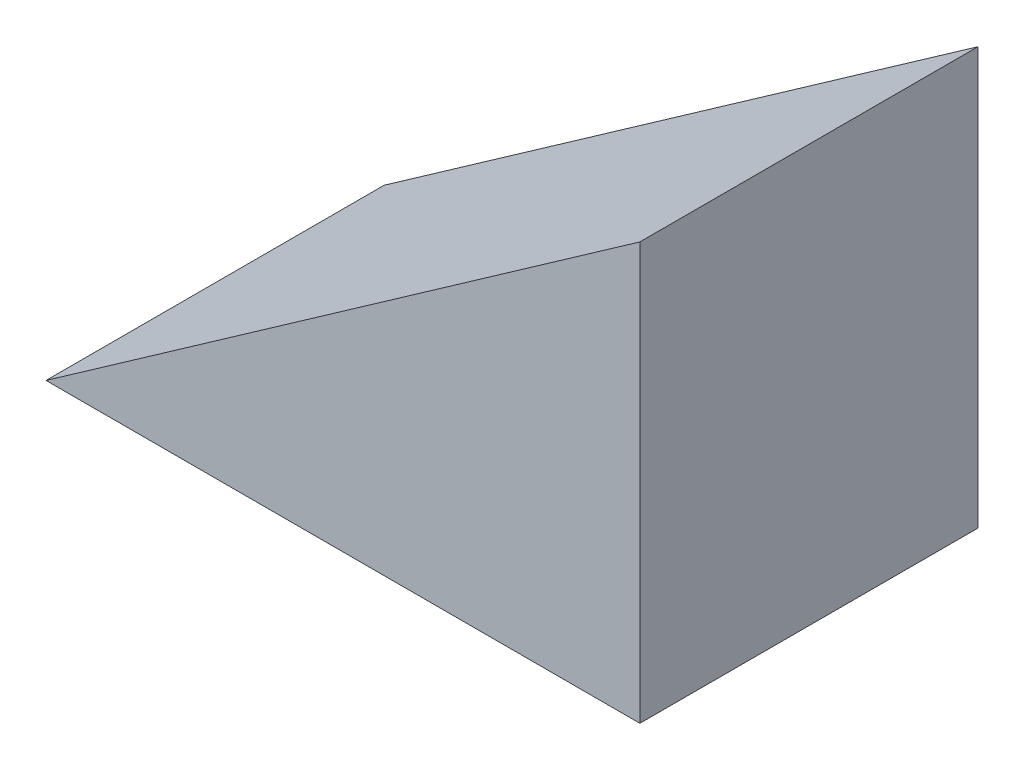
SolidWorks part; units mm, degrees
ref_plane "Front Plane" through (0, 0, 0) normal (0, 0, 1) x (1, 0, 0)
ref_plane "Top Plane" through (0, 0, 0) normal (0, 1, 0) x (1, 0, 0)
ref_plane "Right Plane" through (0, 0, 0) normal (1, 0, 0) x (0, 0, -1)
sketch "Sketch1" plane through (0, 0, 0) normal (0, 1, 0) x (1, 0, 0)
  line L1 (-52.25, -29.75) -> (52.25, -29.75)
  line L2 (-52.25, -29.75) -> (-52.25, 29.75)
  line L3 (-52.25, 29.75) -> (52.25, 29.75)
  line L4 (52.25, -29.75) -> (52.25, 29.75)
  line L5 (-52.25, -29.75) -> (52.25, 29.75) construction
  line L6 (-52.25, 29.75) -> (52.25, -29.75) construction
  point P0 (0, 0)
  dimension "D1" = 104.5
  dimension "D2" = 59.5
extrude "Boss-Extrude1" add sketch "Sketch1" along normal blind 73.36
sketch "Sketch6" plane through (0, 0, 29.75) normal (0, 0, 1) x (1, 0, 0)
  line L0 (-52.25, 0) -> (52.25, 73.36)
  line L1 (-52.25, 0) -> (-52.25, 73.36)
  line L2 (-52.25, 73.36) -> (52.25, 73.36)
extrude "Cut-Extrude2" cut sketch "Sketch6" against normal through all
ref_plane "Plane1" through (-5.7578, 8.2018, 0) normal (-0.5746, 0.8185, 0) x (0.8185, 0.5746, 0)
